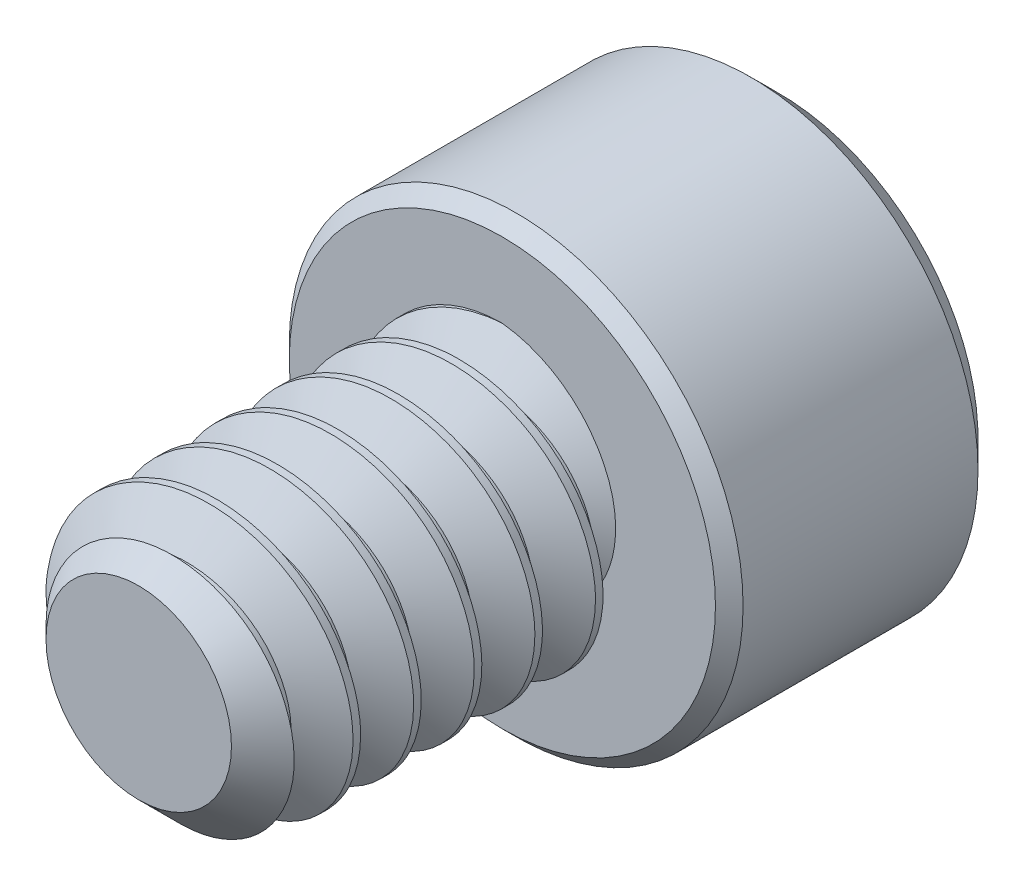
SolidWorks part; units mm, degrees
ref_plane "Front Plane" through (0, 0, 0) normal (0, 0, 1) x (1, 0, 0)
ref_plane "Top Plane" through (0, 0, 0) normal (0, 1, 0) x (1, 0, 0)
ref_plane "Right Plane" through (0, 0, 0) normal (1, 0, 0) x (0, 0, -1)
sketch "Sketch1" plane through (0, 0, 0) normal (0, 0, 1) x (1, 0, 0)
  line L0 (0, 2.413) -> (0, -2.413) construction
  circle A0 centre (0, 0) radius 2.413
  dimension "OD" = 4.826
extrude "Extrude1" add sketch "Sketch1" against normal blind 6.35
sketch "Sketch2" plane through (0, 0, 0) normal (0, 0, 1) x (1, 0, 0)
  circle A0 centre (0, 0) radius 2.413 construction
  circle A1 centre (0, 0) radius 2.413
curve "Helix/Spiral1" pitch 1.0583 height 7.4083 turns 7 parameters "pitch"=1.0583
chamfer "Chamfer3" distance 0.7937 angle 45 1 edges at (2.413, 0, 0)
sketch "Sketch3" plane through (0, 0, 0) normal (1, 0, 0) x (0, 0, -1)
  line L0 (-0.926, 2.413) -> (-0.5292, 1.7256)
  line L1 (-0.5292, 1.7256) -> (-0.3969, 1.7256)
  line L2 (-0.3969, 1.7256) -> (0, 2.413)
  line L3 (-0.926, 2.413) -> (0, 2.413)
  line L4 (-0.463, 2.413) -> (-0.463, 1.7256) construction
  line L5 (-0.7276, 2.0693) -> (-0.1984, 2.0693) construction
  line L6 (0, 2.413) -> (0, -2.413) construction
  dimension "D1" = 0.1323
  dimension "D2" = 0.5292
  dimension "D3" = 60
sweep "Cut-Sweep1" cut profiles "Sketch3" path "Helix/Spiral1"
sketch "Sketch6" plane through (0, 0, -6.35) normal (0, 0, -1) x (-1, 0, 0)
  circle A0 centre (0, 0) radius 3.9624
  dimension "head dia" = 7.9248
extrude "Extrude2" add sketch "Sketch6" along normal blind 4.826
sketch "Sketch7" plane through (0, 0, -11.176) normal (0, 0, -1) x (-1, 0, 0)
  line L1 (0, 2.2914) -> (-1.9844, 1.1457)
  line L2 (-1.9844, 1.1457) -> (-1.9844, -1.1457)
  line L3 (-1.9844, -1.1457) -> (0, -2.2914)
  line L4 (0, -2.2914) -> (1.9844, -1.1457)
  line L5 (1.9844, -1.1457) -> (1.9844, 1.1457)
  line L6 (1.9844, 1.1457) -> (0, 2.2914)
  circle A0 centre (0, 0) radius 1.9844 construction
  dimension "hex dia" = 3.9688
extrude "Cut-Extrude1" cut sketch "Sketch7" against normal blind 2.9766
sketch "Sketch8" plane through (0, 0, -11.176) normal (0, 0, -1) x (-1, 0, 0)
  circle A0 centre (0, 0) radius 2.2914
extrude "Cut-Extrude2" cut sketch "Sketch8" against normal blind 0.4826 draft 45
chamfer "Chamfer1" distance 0.4826 angle 45 1 edges at (-3.9624, 0, -11.176)
chamfer "Chamfer2" distance 0.2413 angle 45 1 edges at (-3.9624, 0, -6.35)
sketch "Sketch9" plane through (0, 0, 0) normal (1, 0, 0) x (0, 0, -1)
  line L0 (0, 2.413) -> (0, -2.413) construction
  line L1 (5.8208, 2.413) -> (5.8208, -2.413) construction
  line L2 (6.35, 3.9624) -> (6.35, -3.9624) construction
  line L3 (11.176, 3.9624) -> (11.176, -3.9624) construction
  line L4 (11.176, 0) -> (0, 0) construction
  dimension "D1" = 5.8208
  dimension "D2" = 4.826
  dimension "D3" = 7.9248
  dimension "D4" = 6.35
equation "\"D3@Helix/Spiral1\" = \"screw length@Extrude1\"+\"pitch@Helix/Spiral1\""
equation "\"D1@Sketch3\" = \"pitch@Helix/Spiral1\"*.125"
equation "\"D2@Sketch3\" = \"pitch@Helix/Spiral1\"*.5"
equation "\"D1@Cut-Extrude1\" = \"hex dia@Sketch7\"*.75"
equation "\"D1@Chamfer1\" = \"head depth@Extrude2\"/10"
equation "\"D1@Sketch9\" = \"pitch@Helix/Spiral1\"*5.5"
equation "\"D1@Chamfer2\" = \"D1@Chamfer1\"/2"
equation "\"D1@Cut-Extrude2\" = \"D1@Chamfer2\"*2"
equation "\"D1@Chamfer3\" = \"pitch@Helix/Spiral1\"*.750"
equation "\"D2@Sketch9\" = \"head depth@Extrude2\""
equation "\"D3@Sketch9\" = \"head dia@Sketch6\""
equation "\"D4@Sketch9\" = \"screw length@Extrude1\""
